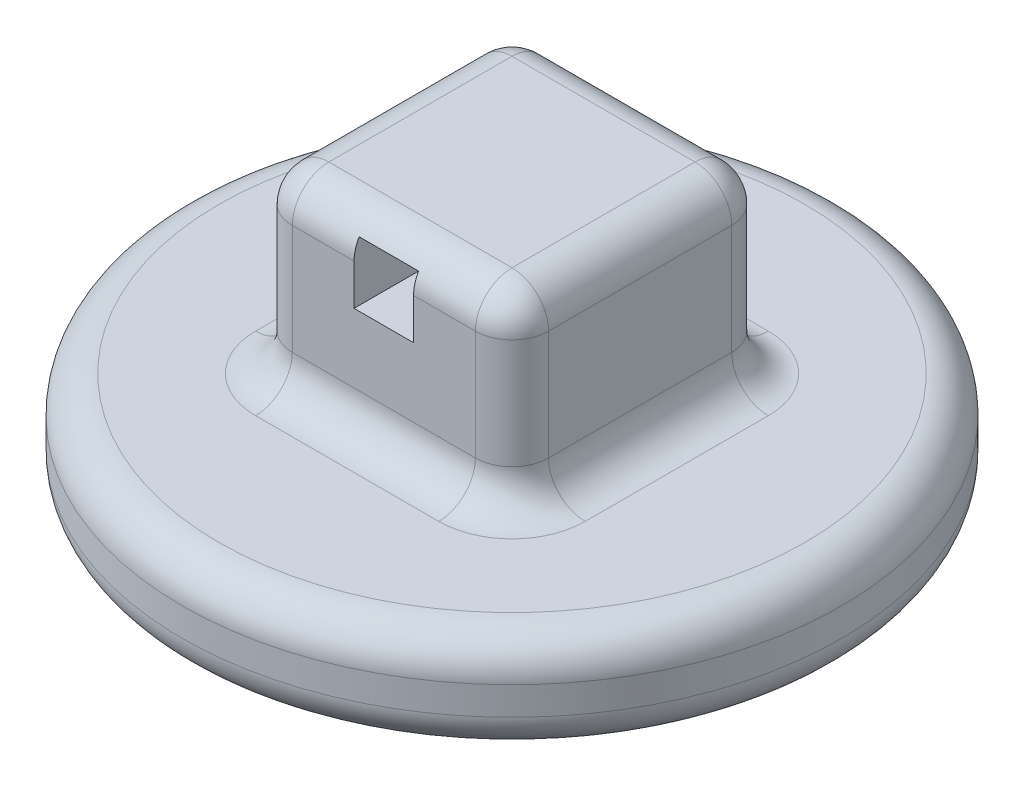
SolidWorks part; units mm, degrees
ref_plane "Front Plane" through (0, 0, 0) normal (0, 0, 1) x (1, 0, 0)
ref_plane "Top Plane" through (0, 0, 0) normal (0, 1, 0) x (1, 0, 0)
ref_plane "Right Plane" through (0, 0, 0) normal (1, 0, 0) x (0, 0, -1)
sketch "Sketch2" plane through (0, 0, 0) normal (0, 1, 0) x (1, 0, 0)
  circle A0 centre (0, 0) radius 18
  dimension "D1" = 36
extrude "Boss-Extrude1" add sketch "Sketch2" along normal blind 3.3
sketch "Sketch3" plane through (0, 3.3, 0) normal (0, 1, 0) x (1, 0, 0)
  line L1 (-7, 7) -> (7, 7)
  line L2 (-7, 7) -> (-7, -7)
  line L3 (-7, -7) -> (7, -7)
  line L4 (7, 7) -> (7, -7)
  line L5 (-7, 7) -> (7, -7) construction
  line L6 (-7, -7) -> (7, 7) construction
  point P0 (0, 0)
  dimension "D1" = 14
  dimension "D2" = 14
extrude "Boss-Extrude2" add sketch "Sketch3" along normal blind 10
sketch "Sketch7" plane through (0, 0, -7) normal (0, 0, -1) x (-1, 0, 0)
  line L0 (-7, 13.3) -> (7, 13.3) construction
  circle A0 centre (0, 8.3145) radius 2.35
  dimension "D1" = 4.9855
sketch "Sketch8" plane through (0, 0, 0) normal (0, -1, 0) x (1, 0, 0)
  circle A0 centre (0, 0) radius 15
  circle A1 centre (0, 0) radius 18 construction
  dimension "D1" = 3
extrude "Cut-Extrude1" [suppressed] cut sketch "Sketch7" against normal blind 8
fillet "Fillet1" [suppressed] radius 8
fillet "Fillet2" [suppressed] radius 2
sketch "Sketch11" plane through (0, 3.3, 0) normal (0, 1, 0) x (1, 0, 0)
  circle A0 centre (0, 0) radius 7.5
  dimension "D1" = 15
sketch "Sketch12" plane through (0, 0, 0) normal (0, -1, 0) x (1, 0, 0)
  circle A0 centre (0, 0) radius 1.725
  dimension "D1" = 3.45
extrude "Cut-Extrude2" cut sketch "Sketch12" against normal blind 10
fillet "Fillet5" [suppressed] radius 1
ref_plane "Plane1" through (0, 13.3, 0) normal (0, 1, 0) x (1, 0, 0)
sketch "Sketch10" plane through (0, 13.3, 0) normal (0, 1, 0) x (1, 0, 0)
  circle A0 centre (0, 0) radius 1.224 construction
sketch "Sketch13" plane through (0, 0, 0) normal (0, -1, 0) x (1, 0, 0)
  circle A0 centre (0, 0) radius 5.075
  dimension "D1" = 10.15
extrude "Cut-Extrude4" cut sketch "Sketch13" against normal blind 3 contours A0
fillet "Fillet6" [suppressed] radius 2
sketch "Sketch17" plane through (0, 0, 0) normal (0, -1, 0) x (1, 0, 0)
  circle A0 centre (0, 0) radius 11.645 construction
  circle A1 centre (0, 0) radius 9.405
  circle A2 centre (0, 0) radius 13.885
  circle A3 centre (0, 0) radius 18
  circle M6 centre (0, 0) radius 5.075
  circle M9 centre (0, 0) radius 18
  dimension "D1" = 23.29
  dimension "D2" = 2.24
  dimension "D3" = 2.24
extrude "Boss-Extrude3" add sketch "Sketch17" along normal blind 2.24 contours A2 M9 | A1 M6 region at (-9.139, 0, 0) region at (-17.4909, 0, 0)
sketch "Sketch14" plane through (0, 0, 0) normal (0, 0, 1) x (1, 0, 0)
  line L0 (-18, 0) -> (18, 0) construction
  line L2 (13, 0) -> (13, -1.5) construction
  line L3 (6.5, 0) -> (9.5, 0)
  line L4 (8, 0) -> (8, -2.5) construction
  line L5 (0, 8.7546) -> (0, -6.2793) construction
  line L6 (13, -1.5) -> (18, -1.5)
  line L7 (18, -1.5) -> (18, 0)
  line L8 (12, 0) -> (18, 0)
  spline S0 degree 2 poles (13, -1.5) (12.5, -1.5) (12, 0) knots 0.5 0.5 0.5 1 1 1
  spline S1 degree 2 poles (9.5, 0) (8, -5) (6.5, 0) knots 0 0 0 1 1 1
  point P9 (12, 0)
  dimension "D1" = 8
  dimension "D2" = 1
  dimension "D3" = 5
  dimension "D4" = 3
  dimension "D5" = 1.5
  dimension "D6" = 2.5
  dimension "D8" = 6
fillet "Fillet8" radius 2.24 2 edges at (0, 0, -13.885) (0, 0, 9.405)
sketch "Sketch16" plane through (0, 0, 0) normal (0, 0, 1) x (1, 0, 0)
  line L0 (18, -1.5) -> (18, 0) construction
  line L1 (12, 0) -> (18, 0) construction
  line L2 (13, -1.5) -> (18, -1.5) construction
  line L3 (18, -1.5) -> (18, 0)
  line L4 (12, 0) -> (18, 0)
  line L5 (13, -1.5) -> (18, -1.5)
  parabola Q0 (13, -1.5) -> (12, 0) focus (13, -1.3333) apex (13, -1.5) construction
  parabola Q1 (13, -1.5) -> (12, 0) focus (13, -1.3333) apex (13, -1.5)
fillet "Fillet7" radius 2 1 edges at (0, 3, -5.075)
sketch "Sketch21" plane through (0, 0, -7) normal (0, 0, -1) x (-1, 0, 0)
  line L1 (-7, 13.3) -> (7, 13.3) construction
  line L2 (-7, 13.3) -> (-7, 3.3) construction
  line L3 (-1.625, 12.315) -> (1.625, 12.315)
  line L4 (-1.625, 12.315) -> (-1.625, 9.065)
  line L5 (-1.625, 9.065) -> (1.625, 9.065)
  line L6 (1.625, 12.315) -> (1.625, 9.065)
  line L7 (-1.625, 12.315) -> (1.625, 9.065) construction
  line L8 (-1.625, 9.065) -> (1.625, 12.315) construction
  circle A0 centre (0, 10.69) radius 1.625 construction
  point P10 (0, 9.065)
  point P11 (-1.625, 10.69)
  dimension "D1" = 3.25
  dimension "D2" = 2.61
  dimension "D3" = 7
extrude "Cut-Extrude6" cut sketch "Sketch21" against normal blind 4
mirror "Mirror2" about plane through (0, 0, 0) normal (0, 0, 1) of "Cut-Extrude6"
fillet "Fillet9" radius 2 14 edges at (7, 3.3, 0) (0, 3.3, -7) (0, 3.3, 7) (0, 13.3, 7) (-7, 13.3, 0) (0, 13.3, -7) (7, 13.3, 0) (-7, 3.3, 0) (0, -2.24, -18) (0, 3.3, 18) (7, 8.3, 7) (-7, 8.3, 7) (7, 8.3, -7) (-7, 8.3, -7)
sketch "Sketch19" [suppressed] plane through (0, 0, -7) normal (0, 0, -1) x (-1, 0, 0)
  circle A1 centre (0, 97.76) radius 2.05
  circle A2 centre (0, 97.76) radius 2.05
  circle A3 centre (0, 10.69) radius 1.55
  circle A4 centre (0, 10.69) radius 1.55
  dimension "D3" = 3.1
  dimension "D1" = 0
  dimension "D2" = 0
sketch "Sketch22" plane through (0, 0, -7) normal (0, 0, -1) x (-1, 0, 0)
  line L0 (-5, 11.3) -> (-5, 5.3) construction
  line L1 (-5, 5.3) -> (5, 5.3) construction
  circle A1 centre (0, 10.69) radius 1.57
  dimension "D1" = 3.14
  dimension "D2" = 5
  dimension "D3" = 5.39
equation "\"D1@Boss-Extrude2\"=10"
equation "\"D1@Sketch17\"=2*(2.24+9.405)"
equation "\"D2@Sketch3\"=\"D1@Sketch3\""
equation "\"D2@Sketch21\"=4-1.39"
